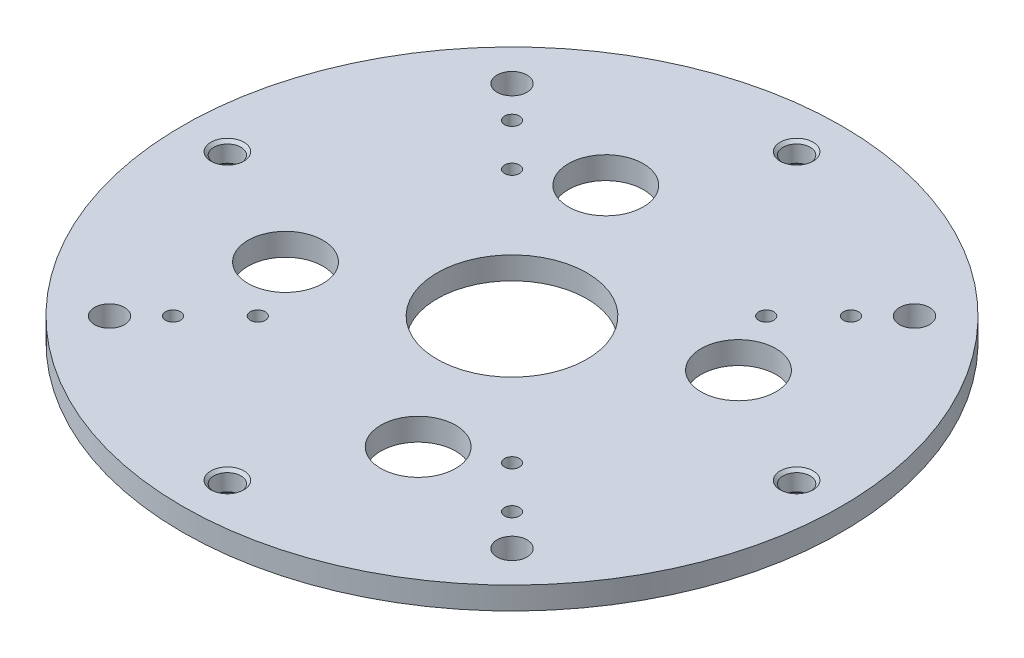
SolidWorks part; units mm, degrees
material "6061-T4 (SS)"
ref_plane "Front Plane" through (0, 0, 0) normal (0, 0, 1) x (1, 0, 0)
ref_plane "Top Plane" through (0, 0, 0) normal (0, 1, 0) x (1, 0, 0)
ref_plane "Right Plane" through (0, 0, 0) normal (1, 0, 0) x (0, 0, -1)
sketch "Sketch2" plane through (0, 0, 0) normal (0, 1, 0) x (1, 0, 0)
  line L0 (0, 0) -> (0, 114.3) construction
  line L3 (22.4506, 22.4506) -> (98.7828, 98.7828) construction
  line L4 (61.9546, 26.0336) -> (81.4605, 45.5395)
  line L5 (26.0336, 61.9546) -> (45.5395, 81.4605)
  line L7 (61.9546, -26.0336) -> (81.4605, -45.5395)
  line L8 (4.4901, 40.4112) -> (80.8223, 116.7433) construction
  line L9 (40.4112, 4.4901) -> (116.7433, 80.8223) construction
  line L10 (26.0336, -61.9546) -> (45.5395, -81.4605)
  line L11 (-26.0336, -61.9546) -> (-45.5395, -81.4605)
  line L12 (-61.9546, -26.0336) -> (-81.4605, -45.5395)
  line L13 (-61.9546, 26.0336) -> (-81.4605, 45.5395)
  line L14 (-26.0336, 61.9546) -> (-45.5395, 81.4605)
  arc A0 (-91.6807, 43.786) -> (-91.6807, -43.786) centre (0, 0) ccw
  circle A1 centre (0, 0) radius 139.7
  arc A2 (43.786, 91.6807) -> (-43.786, 91.6807) centre (0, 0) ccw
  arc A3 (91.6807, -43.786) -> (91.6807, 43.786) centre (0, 0) ccw
  arc A4 (-43.786, -91.6807) -> (43.786, -91.6807) centre (0, 0) ccw
  arc A5 (-19.585, -60.4043) -> (19.585, -60.4043) centre (0, 0) ccw
  arc A6 (-81.4605, 45.5395) -> (-91.6807, 43.786) centre (-85.9506, 41.0494) ccw
  arc A7 (-91.6807, -43.786) -> (-81.4605, -45.5395) centre (-85.9506, -41.0494) ccw
  arc A8 (-45.5395, -81.4605) -> (-43.786, -91.6807) centre (-41.0494, -85.9506) ccw
  arc A9 (43.786, -91.6807) -> (45.5395, -81.4605) centre (41.0494, -85.9506) ccw
  arc A10 (60.4043, -19.585) -> (60.4043, 19.585) centre (0, 0) ccw
  arc A11 (19.585, 60.4043) -> (-19.585, 60.4043) centre (0, 0) ccw
  arc A12 (81.4605, -45.5395) -> (91.6807, -43.786) centre (85.9506, -41.0494) ccw
  arc A13 (91.6807, 43.786) -> (81.4605, 45.5395) centre (85.9506, 41.0494) ccw
  arc A14 (-60.4043, -19.585) -> (-61.9546, -26.0336) centre (-66.4447, -21.5435) cw
  arc A15 (45.5395, 81.4605) -> (43.786, 91.6807) centre (41.0494, 85.9506) ccw
  arc A16 (-43.786, 91.6807) -> (-45.5395, 81.4605) centre (-41.0494, 85.9506) ccw
  arc A17 (-60.4043, 19.585) -> (-60.4043, -19.585) centre (0, 0) ccw
  circle A18 centre (0, 0) radius 31.75
  arc A19 (-26.0336, -61.9546) -> (-19.585, -60.4043) centre (-21.5435, -66.4447) cw
  arc A20 (19.585, -60.4043) -> (26.0336, -61.9546) centre (21.5435, -66.4447) cw
  arc A21 (61.9546, -26.0336) -> (60.4043, -19.585) centre (66.4447, -21.5435) cw
  arc A22 (60.4043, 19.585) -> (61.9546, 26.0336) centre (66.4447, 21.5435) cw
  arc A23 (26.0336, 61.9546) -> (19.585, 60.4043) centre (21.5435, 66.4447) cw
  arc A24 (-19.585, 60.4043) -> (-26.0336, 61.9546) centre (-21.5435, 66.4447) cw
  arc A25 (-61.9546, 26.0336) -> (-60.4043, 19.585) centre (-66.4447, 21.5435) cw
  point P28 (-51.6003, -87.5213)
  point P29 (0, 0)
  point P39 (87.5213, -51.6003)
  point P43 (-23.1922, -59.1132)
  point P47 (51.6003, 87.5213)
  point P52 (23.1922, -59.1132)
  point P55 (59.1132, -23.1922)
  point P58 (59.1132, 23.1922)
  point P61 (23.1922, 59.1132)
  dimension "D2" = 279.4
  dimension "D5" = 127
  dimension "D4" = 203.2
  dimension "D9" = 63.5
  dimension "D10" = 6.35
  dimension "D13" = 6.35
  dimension "D3" = 45
  dimension "D8" = 50.8
  dimension "D11" = 66.4447
  dimension "D12" = 66.4447
  dimension "D6" = 25.4
  dimension "D7" = 4
extrude "Boss-Extrude1" add sketch "Sketch2" along normal blind 9.525
sketch "Sketch3" plane through (0, 9.525, 0) normal (0, 1, 0) x (1, 0, 0)
  line L0 (0, 0) -> (0, 120.65) construction
  line L1 (0, 0) -> (85.3124, 85.3124) construction
  line L2 (85.3124, 85.3124) -> (103.2729, 103.2729) construction
  line L3 (0, 0) -> (-53.8815, 53.8815) construction
  line L4 (-53.8815, 53.8815) -> (-71.842, 71.842) construction
  circle A0 centre (-71.842, 71.842) radius 3.175
  circle A1 centre (0, 0) radius 120.65 construction
  circle A2 centre (0, 120.65) radius 7.1437
  circle A3 centre (120.65, 0) radius 7.1438
  circle A4 centre (0, -120.65) radius 7.1437
  circle A5 centre (-120.65, 0) radius 7.1438
  circle A6 centre (0, 0) radius 120.65 construction
  circle A10 centre (0, 0) radius 139.7 construction
  circle A17 centre (-53.8815, 53.8815) radius 3.175
  circle A18 centre (-71.842, -71.842) radius 3.175
  circle A19 centre (71.842, -71.842) radius 3.175
  circle A20 centre (71.842, 71.842) radius 3.175
  circle A21 centre (53.8815, 53.8815) radius 3.175
  circle A22 centre (53.8815, -53.8815) radius 3.175
  circle A23 centre (-53.8815, -53.8815) radius 3.175
  circle A24 centre (85.3124, 85.3124) radius 6.35
  circle A25 centre (85.3124, -85.3124) radius 6.35
  circle A26 centre (-85.3124, -85.3124) radius 6.35
  circle A27 centre (-85.3124, 85.3124) radius 6.35
  point P17 (0, 0)
  point P26 (0, 0)
  point P39 (0, 0)
  point P47 (0, 0)
  point P54 (0, 0)
  point P63 (0, 0)
  dimension "D2" = 14.2875
  dimension "D5" = 120.65
  dimension "D6" = 76.2
  dimension "D7" = 241.3
  dimension "D9" = 25.4
  dimension "D13" = 12.7
  dimension "D14" = 45
  dimension "D15" = 4
  dimension "D4" = 45
  dimension "D3" = 4
  dimension "D11" = 4
  dimension "D12" = 4
extrude "Cut-Extrude2" cut sketch "Sketch3" against normal through all contours A24 | A25 | A26 | A27 | A0 | A17 | A20 | A21 | A19 | A22 | A18 | A23
sketch "Sketch4" plane through (0, 9.525, 0) normal (0, 1, 0) x (1, 0, 0)
  line L1 (-152.4, -152.4) -> (152.4, -152.4) construction
  line L2 (-152.4, -152.4) -> (-152.4, 152.4) construction
  line L3 (-152.4, 152.4) -> (152.4, 152.4) construction
  line L4 (152.4, -152.4) -> (152.4, 152.4) construction
  line L5 (-152.4, -152.4) -> (152.4, 152.4) construction
  line L6 (-152.4, 152.4) -> (152.4, -152.4) construction
  point P0 (0, 0)
  dimension "D1" = 304.8
sketch "Sketch5" plane through (0, 9.525, 0) normal (0, 1, 0) x (1, 0, 0)
  circle A1 centre (0, 0) radius 139.7
  circle A2 centre (0, 0) radius 139.7
  circle A3 centre (0, -120.65) radius 7.1437
  circle A4 centre (0, -120.65) radius 7.1437
  circle A5 centre (120.65, 0) radius 7.1438
  circle A6 centre (120.65, 0) radius 7.1438
  circle A7 centre (0, 120.65) radius 7.1437
  circle A8 centre (0, 120.65) radius 7.1437
  circle A9 centre (-71.842, 71.842) radius 3.175
  circle A10 centre (-71.842, 71.842) radius 3.175
  circle A11 centre (85.3124, 85.3124) radius 6.35
  circle A12 centre (85.3124, 85.3124) radius 6.35
  circle A13 centre (-53.8815, 53.8815) radius 3.175
  circle A14 centre (-53.8815, 53.8815) radius 3.175
  circle A15 centre (-120.65, 0) radius 7.1438
  circle A16 centre (-120.65, 0) radius 7.1438
  circle A17 centre (71.842, 71.842) radius 3.175
  circle A18 centre (71.842, 71.842) radius 3.175
  circle A19 centre (71.842, -71.842) radius 3.175
  circle A20 centre (71.842, -71.842) radius 3.175
  circle A21 centre (-71.842, -71.842) radius 3.175
  circle A22 centre (-71.842, -71.842) radius 3.175
  circle A23 centre (-85.3124, 85.3124) radius 6.35
  circle A24 centre (-85.3124, 85.3124) radius 6.35
  circle A25 centre (-85.3124, -85.3124) radius 6.35
  circle A26 centre (-85.3124, -85.3124) radius 6.35
  circle A27 centre (85.3124, -85.3124) radius 6.35
  circle A28 centre (85.3124, -85.3124) radius 6.35
  circle A29 centre (-53.8815, -53.8815) radius 3.175
  circle A30 centre (-53.8815, -53.8815) radius 3.175
  circle A31 centre (53.8815, -53.8815) radius 3.175
  circle A32 centre (53.8815, -53.8815) radius 3.175
  circle A33 centre (53.8815, 53.8815) radius 3.175
  circle A34 centre (53.8815, 53.8815) radius 3.175
  dimension "D1" = 0
  dimension "D2" = 0
  dimension "D3" = 0
  dimension "D4" = 0
  dimension "D5" = 0
  dimension "D6" = 0
  dimension "D7" = 0
  dimension "D8" = 0
  dimension "D9" = 0
  dimension "D10" = 0
  dimension "D11" = 0
  dimension "D12" = 0
  dimension "D13" = 0
  dimension "D14" = 0
  dimension "D15" = 0
  dimension "D16" = 0
  dimension "D17" = 0
hole_wizard "1/2-20 Tapped Hole1" positions "Sketch6" profile "Sketch7" tap size "1/2-20" standard "ANSI Inch" end condition through all
sketch "Sketch6" plane through (0, 9.525, 0) normal (0, 1, 0) x (1, 0, 0)
  point P0 (-120.65, 0)
  point P3 (0, 120.65)
  point P6 (120.65, 0)
  point P9 (0, -120.65)
sketch "Sketch7" plane through (-120.65, 9.525, 0) normal (1, 0, 0) x (0, 0, 1)
  line L0 (0, 0) -> (0, 9.525)
  line L1 (0, 9.525) -> (6.985, 9.525)
  line L2 (5.7544, 8.2944) -> (5.7544, 1.2306)
  line L3 (5.7544, 1.2306) -> (6.985, 0)
  line L5 (6.985, 0) -> (0, 0)
  line L6 (-5.7544, 1.2306) -> (-6.985, 0) construction
  line L7 (6.985, 9.525) -> (5.7544, 8.2944)
  line L8 (-6.985, 9.525) -> (-5.7544, 8.2944) construction
  line L11 (0, -6.35) -> (0, 107.95) construction
  dimension "Thru Tap Drill Dia." = 11.5087
  dimension "Thru Tap Drill Depth" = 9.525
  dimension "Near C'Sink Dia." = 13.97
  dimension "Near C'Sink Angle" = 90
  dimension "Far C'Sink Dia." = 13.97
  dimension "Far C'Sink Angle" = 90
cosmetic thread "Hole Thread1" parameters "D2"=12.7
cosmetic thread "Hole Thread2" parameters "D2"=12.7
cosmetic thread "Hole Thread3" parameters "D2"=12.7
cosmetic thread "Hole Thread4" parameters "D2"=12.7
other "Move Face1" [suppressed] flip direction yes offset 9.398 parameters "D1"=9.398
other "delete_cutouts" face at (45.9853, 4.7625, -86.7975) face at (0, 4.7625, -96.6403) face at (35.7865, 4.7625, -71.7076) face at (22.9185, 4.7625, -60.725) face at (0, 4.7625, -61.9522) face at (-22.9185, 4.7625, -60.725) face at (-35.7865, 4.7625, -71.7076) face at (-45.9853, 4.7625, -86.7975) face at (86.7975, 4.7625, 45.9853) face at (96.6403, 4.7625, 0) face at (71.7076, 4.7625, 35.7865) face at (60.725, 4.7625, 22.9185) face at (61.9522, 4.7625, 0) face at (60.725, 4.7625, -22.9185) face at (71.7076, 4.7625, -35.7865) face at (86.7975, 4.7625, -45.9853) face at (-45.9853, 4.7625, 86.7975) face at (0, 4.7625, 96.6403) face at (-35.7865, 4.7625, 71.7076) face at (-22.9185, 4.7625, 60.725) face at (0, 4.7625, 61.9522) face at (22.9185, 4.7625, 60.725) face at (35.7865, 4.7625, 71.7076) face at (45.9853, 4.7625, 86.7975) face at (-86.7975, 4.7625, -45.9853) face at (-96.6403, 4.7625, 0) face at (-71.7076, 4.7625, -35.7865) face at (-60.725, 4.7625, -22.9185) face at (-61.9522, 4.7625, 0) face at (-60.725, 4.7625, 22.9185) face at (-71.7076, 4.7625, 35.7865) face at (-86.7975, 4.7625, 45.9853) and patch yes
sketch "Sketch8" [suppressed] plane through (2.064, -2.6625, -0.8549) normal (0.5939, -0.766, -0.246) x (0.8046, 0.5654, 0.1816)
  circle A0 centre (52.2094, -28.2305) radius 12.7
  dimension "D1" = 25.4
extrude "for38LOXtubing" [suppressed] cut sketch "Sketch8" along normal through all
sketch "Sketch9" [suppressed] plane through (0, 9.525, 0) normal (0, 1, 0) x (1, 0, 0)
  line L0 (48.8813, 20.2473) -> (86.8988, 35.9946) construction
  circle A1 centre (67.8901, 28.121) radius 15.875
  ellipse E0 centre (64.198, 26.5917) end of major axis (48.8813, 20.2473) minor radius 12.7 construction
  ellipse E1 centre (71.5821, 29.6503) end of major axis (56.2654, 23.3059) minor radius 12.7 construction
  dimension "D1" = 31.75
extrude "Cut-Extrude5" [suppressed] cut sketch "Sketch9" against normal through all
other "DeleteFace2" [suppressed]
other "DeleteFace3" [suppressed]
ref_axis "Axis1" through (228.1946, -202.0215, -94.5213) along (-0.5939, 0.766, 0.246)
ref_plane "Plane1" through (0, 4.7625, 0) normal (0, 1, 0) x (1, 0, 0)
ref_point "Point1"
sketch "Sketch13" plane through (0, 0, 0) normal (0, -1, 0) x (1, 0, 0)
  circle A0 centre (67.8901, -28.121) radius 15.875
  dimension "D1" = 31.75
extrude "Cut-Extrude7" cut sketch "Sketch13" against normal through all
pattern_circular "CirPattern1" count 4 over 360 about axis through (0, 9.525, 0) along (0, -1, 0) of "Cut-Extrude7"
